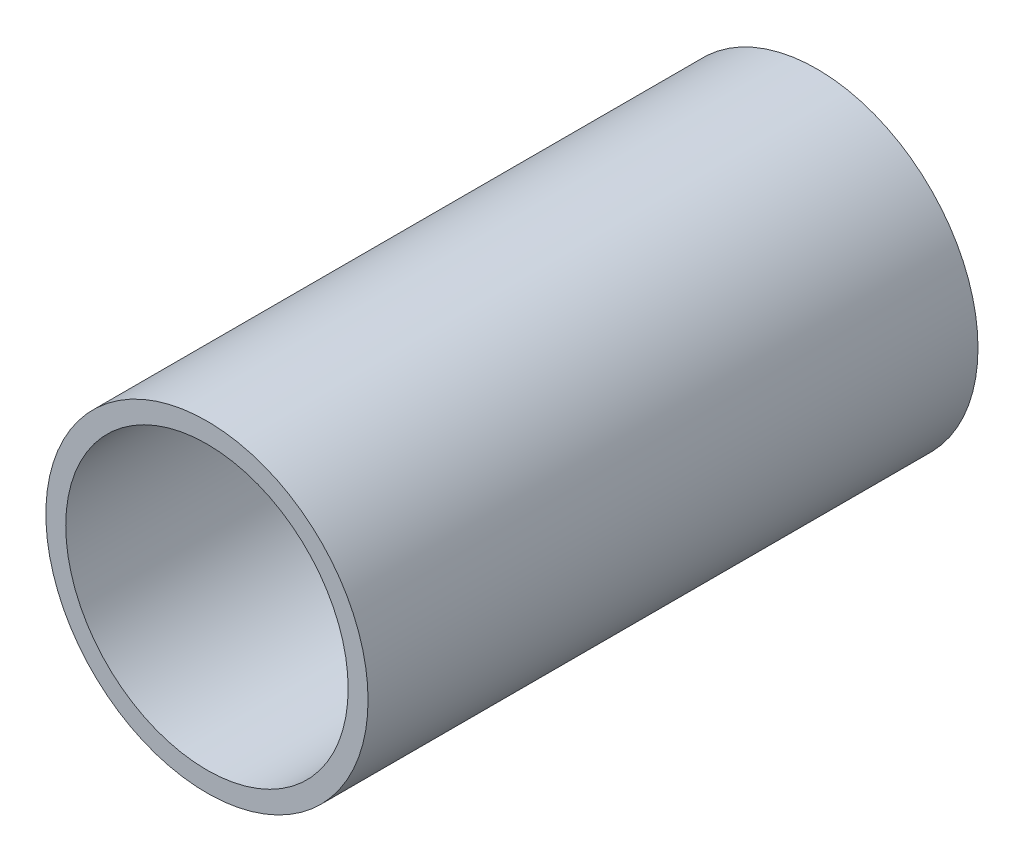
SolidWorks part; units mm, degrees
material "PVC Rígido"
ref_plane "Alzado" through (0, 0, 0) normal (0, 0, 1) x (1, 0, 0)
ref_plane "Planta" through (0, 0, 0) normal (0, 1, 0) x (1, 0, 0)
ref_plane "Vista lateral" through (0, 0, 0) normal (1, 0, 0) x (0, 0, -1)
sketch "Croquis1" plane through (0, 0, 0) normal (0, 0, 1) x (1, 0, 0)
  circle A0 centre (0, 0) radius 10.65
  circle A1 centre (0, 0) radius 12.15
  dimension "D1" = 21.3
  dimension "D2" = 24.3
extrude "Saliente-Extruir1" add sketch "Croquis1" along normal blind 46
thread "Rosca1" pitch 1.9538 method extrude profile "Perfil de rosca1" start angle 0, offset 0, length 19.05, pitch 1.9538, diameter 21.3
ref_plane "Plano1" through (10.65, 0, 0) normal (0, -1, 0) x (1, 0, 0)
sketch "Perfil de rosca1" plane through (10.65, 0, 0) normal (0, -1, 0) x (1, 0, 0)
  line L0 (0, 0) -> (0, 1.9538) construction
  line L11 (0, 0) -> (0, 1.7096)
  line L12 (0, 1.7096) -> (-1.0576, 1.099)
  line L13 (-1.0576, 1.099) -> (-1.0576, 0.6106)
  line L15 (-1.0576, 0.6106) -> (0, 0)
  line L17 (-1.0576, 0.8548) -> (0, 0.8548) construction
  point P2 (0, 0)
  dimension "Pitch" = 1.9538
  dimension "Profile_Angle" = 60
  dimension "Profile_Land" = 0.4885
  dimension "Profile_Height" = 1.0576
